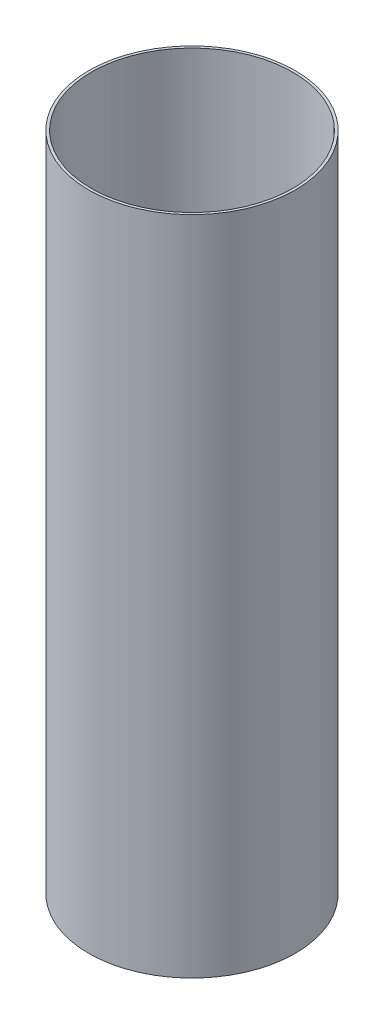
SolidWorks part; units mm, degrees
material "A-Glass Fiber"
ref_plane "Front Plane" through (0, 0, 0) normal (0, 0, 1) x (1, 0, 0)
ref_plane "Top Plane" through (0, 0, 0) normal (0, 1, 0) x (1, 0, 0)
ref_plane "Right Plane" through (0, 0, 0) normal (1, 0, 0) x (0, 0, -1)
sketch "Sketch1" plane through (0, 0, 0) normal (0, 0, 1) x (1, 0, 0)
  line L0 (78.16, 0) -> (78.16, 500)
  line L1 (76.2, 0) -> (76.2, 500)
  line L2 (78.16, 500) -> (76.2, 500)
  line L3 (76.2, 0) -> (78.16, 0)
  line L4 (0, 204.6154) -> (0, 85.8935) construction
  dimension "D1" = 76.2
  dimension "D2" = 500
  dimension "D3" = 1.96
revolve "Revolve1" add sketch "Sketch1" angle 360 about L4
